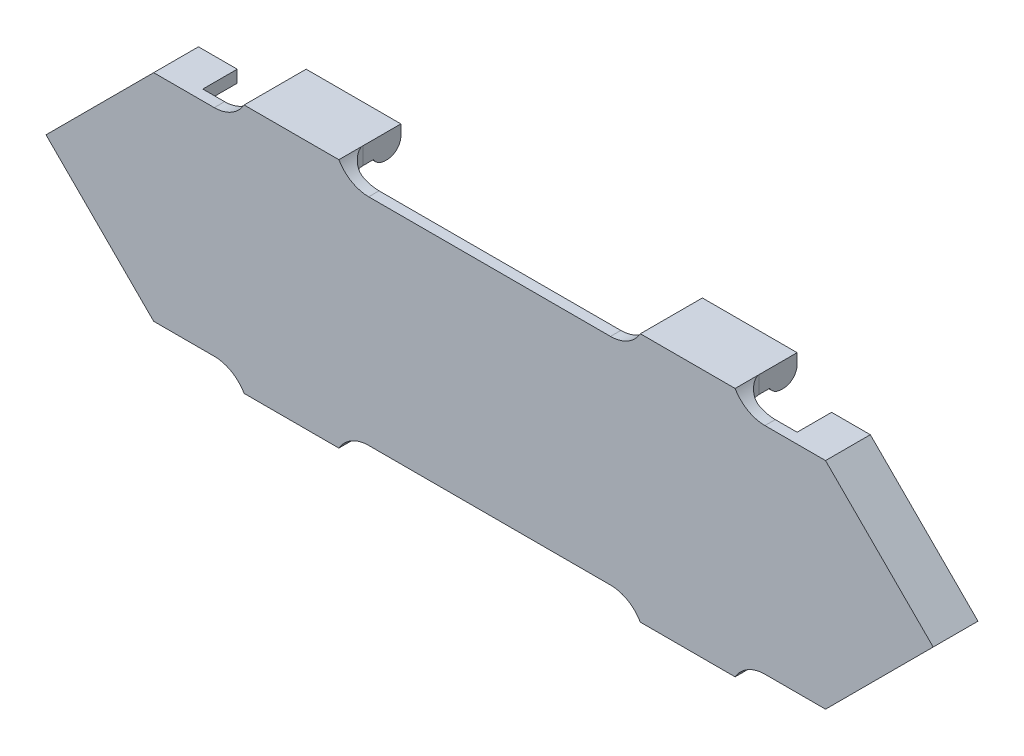
SolidWorks part; units mm, degrees
ref_plane "Front Plane" through (0, 0, 0) normal (0, 0, 1) x (1, 0, 0)
ref_plane "Top Plane" through (0, 0, 0) normal (0, 1, 0) x (1, 0, 0)
ref_plane "Right Plane" through (0, 0, 0) normal (1, 0, 0) x (0, 0, -1)
sketch "Sketch1" plane through (0, 0, 0) normal (0, 0, 1) x (1, 0, 0)
  line L0 (-33.3789, 6.3169) -> (16.1511, 6.3169)
  line L1 (16.1511, 6.3169) -> (24.0886, -1.6206)
  line L2 (24.0886, -1.6206) -> (16.1511, -9.5581)
  line L3 (16.1511, -9.5581) -> (-33.3789, -9.5581)
  line L4 (-33.3789, -9.5581) -> (-41.3164, -1.6206)
  line L5 (-41.3164, -1.6206) -> (-33.3789, 6.3169)
  dimension "D1" = 49.53
  dimension "D2" = 15.875
  dimension "D3" = 135
  dimension "D4" = 135
extrude "Boss-Extrude1" add sketch "Sketch1" along normal blind 0.762
sketch "Sketch2" plane through (0, 0, 0) normal (0, 0, -1) x (-1, 0, 0)
  line L0 (30.5214, 6.3169) -> (33.3789, 6.3169)
  line L1 (30.5214, 5.4188) -> (30.5214, 6.3169)
  line L2 (-16.1511, -9.5581) -> (-24.0886, -1.6206) construction
  line L3 (-24.0886, -1.6206) -> (-16.1511, 6.3169) construction
  line L4 (30.5214, -9.5581) -> (33.3789, -9.5581)
  line L5 (30.5214, -8.6601) -> (30.5214, -9.5581)
  line L6 (-16.1511, -9.5581) -> (-24.0886, -1.6206)
  line L7 (-24.0886, -1.6206) -> (-16.1511, 6.3169)
  line L8 (-15.2531, -8.6601) -> (-22.2925, -1.6206)
  line L9 (-22.2925, -1.6206) -> (-15.2531, 5.4188)
  line L12 (-15.2531, -8.6601) -> (-13.2936, -8.6601)
  line L13 (-13.2936, -8.6601) -> (-13.2936, 5.4188) construction
  line L14 (-13.2936, 5.4188) -> (-15.2531, 5.4188)
  line L15 (8.6139, 6.3169) -> (8.6139, -9.5581) construction
  line L16 (-16.1511, 6.3169) -> (33.3789, 6.3169) construction
  line L17 (33.3789, -9.5581) -> (-16.1511, -9.5581) construction
  line L21 (-13.2936, -8.6601) -> (-13.2936, -9.5581)
  line L22 (-13.2936, -9.5581) -> (-16.1511, -9.5581)
  line L23 (-13.2936, 5.4188) -> (-13.2936, 6.3169)
  line L24 (-13.2936, 6.3169) -> (-16.1511, 6.3169)
  line L25 (30.5214, 5.4188) -> (32.4809, 5.4188)
  line L26 (32.4809, -8.6601) -> (30.5214, -8.6601)
  line L27 (39.5204, -1.6206) -> (32.4809, 5.4188)
  line L28 (32.4809, -8.6601) -> (39.5204, -1.6206)
  line L29 (41.3164, -1.6206) -> (33.3789, 6.3169)
  line L30 (33.3789, -9.5581) -> (41.3164, -1.6206)
  dimension "D2" = 21.9075
  dimension "D1" = 1.27
extrude "Boss-Extrude2" add sketch "Sketch2" along normal blind 2.54
ref_plane "Plane1" through (13.2936, 6.3169, 0) normal (-1, 0, 0) x (0, 0, 1)
sketch "Sketch4" plane through (0, 6.3169, 0) normal (0, 1, 0) x (1, 0, 0)
  line L0 (9.4836, -0.762) -> (2.4986, -0.762)
  line L1 (13.2936, 0) -> (-30.5214, 0) construction
  line L2 (2.4986, -0.762) -> (2.4986, 3.81)
  line L3 (2.4986, 3.81) -> (9.4836, 3.81)
  line L4 (-8.6139, -0.762) -> (-8.6139, 0) construction
  line L5 (16.1511, -0.762) -> (-33.3789, -0.762) construction
  line L6 (9.4836, -0.762) -> (9.4836, 3.81)
  line L7 (13.2936, 2.54) -> (13.2936, 0) construction
  line L8 (-26.7114, -0.762) -> (-26.7114, 3.81)
  line L9 (-19.7264, 3.81) -> (-26.7114, 3.81)
  line L10 (-19.7264, -0.762) -> (-19.7264, 3.81)
  line L11 (-26.7114, -0.762) -> (-19.7264, -0.762)
  dimension "D1" = 3.81
  dimension "D2" = 6.985
  dimension "D3" = 3.81
extrude "Boss-Extrude3" add sketch "Sketch4" along normal blind 1.27
fillet "Fillet1" radius 2.54 4 edges at (-26.7114, 6.3169, 0.381) (-19.7264, 6.3169, 0.381) (2.4986, 6.3169, 0.381) (9.4836, 6.3169, 0.381)
sketch "Sketch5" plane through (0, 6.3169, 0) normal (0, -1, 0) x (1, 0, 0)
  line L0 (9.4836, 0) -> (9.4836, -3.81) construction
  line L1 (2.4986, -3.81) -> (9.4836, -3.81)
  line L2 (2.4986, -3.81) -> (2.4986, -1.778)
  line L3 (2.4986, -1.778) -> (9.4836, -1.778)
  line L4 (9.4836, -3.81) -> (9.4836, -1.778)
  line L5 (-19.7264, 0) -> (-19.7264, -3.81) construction
  line L6 (-26.7114, -3.81) -> (-19.7264, -3.81)
  line L7 (-26.7114, -3.81) -> (-26.7114, -1.778)
  line L8 (-26.7114, -1.778) -> (-19.7264, -1.778)
  line L9 (-19.7264, -3.81) -> (-19.7264, -1.778)
  dimension "D1" = 2.032
  dimension "D2" = 2.032
extrude "Boss-Extrude4" add sketch "Sketch5" along normal blind 0.508
fillet "Fillet2" radius 1.016 4 edges at (5.9911, 5.8089, -3.81) (5.9911, 5.8089, -1.778) (-23.2189, 5.8089, -3.81) (-23.2189, 5.8089, -1.778)
fillet "Fillet3" radius 1.016 4 edges at (-26.7114, 6.9519, 0) (2.4986, 6.9519, 0) (-19.7264, 6.9519, 0) (9.4836, 6.9519, 0)
ref_plane "Plane2" through (0, -1.6206, 0) normal (0, 1, 0) x (1, 0, 0)
mirror "Mirror4" about plane through (0, -1.6206, 0) normal (0, 1, 0) of "Boss-Extrude3", "Fillet2", "Boss-Extrude4"
fillet "Fillet4" radius 2.54 4 edges at (-26.7114, -9.5581, 0.381) (9.4836, -9.5581, 0.381) (-19.7264, -9.5581, 0.381) (2.4986, -9.5581, 0.381)
fillet "Fillet5" radius 1.016 4 edges at (-26.7114, -10.1931, 0) (-19.7264, -10.1931, 0) (2.4986, -10.1931, 0) (9.4836, -10.1931, 0)
